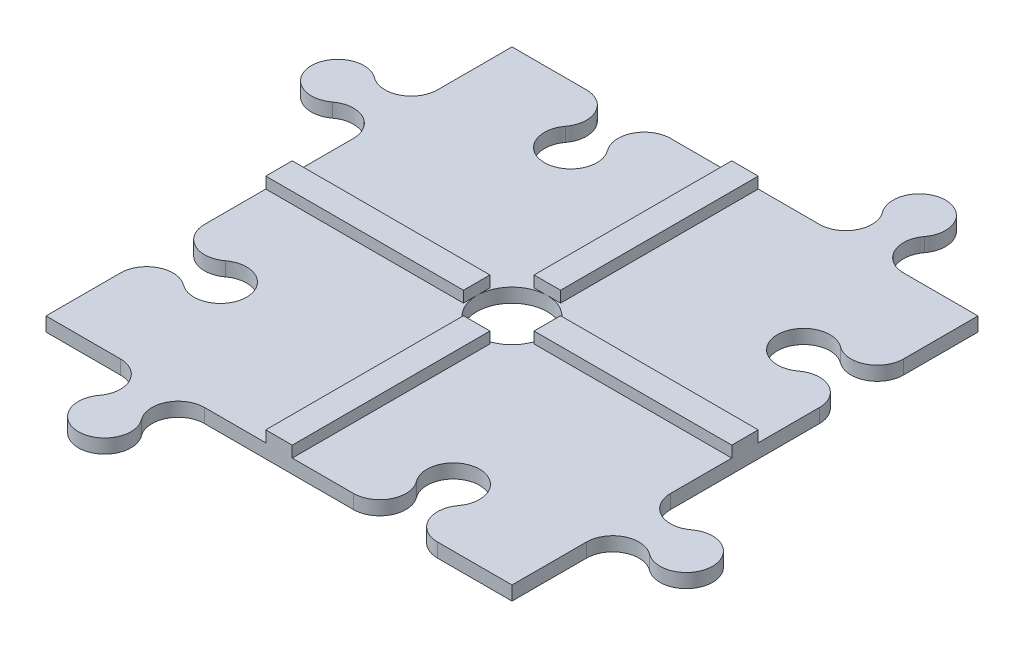
SolidWorks part; units mm, degrees
note: The reader was unsure of these and kept them because the rebuilt part matched: shared geometry of "Sketch2<3>".
ref_plane "Front Plane" through (0, 0, 0) normal (0, 0, 1) x (1, 0, 0)
ref_plane "Top Plane" through (0, 0, 0) normal (0, 1, 0) x (1, 0, 0)
ref_plane "Right Plane" through (0, 0, 0) normal (1, 0, 0) x (0, 0, -1)
sketch "Sketch1" plane through (0, 0, 0) normal (0, 1, 0) x (1, 0, 0)
  line L1 (52.7929, -52.7929) -> (-52.7929, -52.7929)
  line L2 (52.7929, -52.7929) -> (52.7929, 52.7929)
  line L3 (52.7929, 52.7929) -> (-52.7929, 52.7929)
  line L4 (-52.7929, -52.7929) -> (-52.7929, 52.7929)
  line L5 (52.7929, -52.7929) -> (-52.7929, 52.7929) construction
  line L6 (52.7929, 52.7929) -> (-52.7929, -52.7929) construction
  circle A0 centre (0, 0) radius 52.7929 construction
  circle A1 centre (0, 0) radius 52.7929 construction
  dimension "D1" = 105.5858
extrude "Boss-Extrude1" add sketch "Sketch1" along normal blind 3.175 contours L4 L3 L2 L1
sketch "Sketch2" plane through (0, 0, 0) normal (0, 1, 0) x (1, 0, 0)
  line L0 (-52.7929, 26.3965) -> (-113.1129, 26.3965) construction
  line L1 (-52.7929, 35.9215) -> (-52.7929, 16.8715)
  line L2 (-52.7929, -52.7929) -> (-52.7929, 52.7929) construction
  line L3 (0, 0) -> (-52.7929, 0) construction
  line L4 (52.7929, 52.7929) -> (-52.7929, -52.7929) construction
  line L5 (-52.7929, -35.9215) -> (-52.7929, -16.8715)
  arc A0 (-62.3179, 21.634) -> (-71.8429, 26.3965) centre (-65.8898, 26.3965) cw
  arc A1 (-62.3179, 21.634) -> (-52.7929, 16.8715) centre (-58.746, 16.8715) cw
  arc A2 (-62.3179, 31.159) -> (-52.7929, 35.9215) centre (-58.746, 35.9215) ccw
  arc A3 (-62.3179, -21.634) -> (-52.7929, -16.8715) centre (-58.746, -16.8715) ccw construction
  arc A4 (-62.3179, 31.159) -> (-71.8429, 26.3965) centre (-65.8898, 26.3965) ccw
  arc A5 (-62.3179, -21.634) -> (-71.8429, -26.3965) centre (-65.8898, -26.3965) ccw construction
  arc A6 (-62.3179, -31.159) -> (-71.8429, -26.3965) centre (-65.8898, -26.3965) cw construction
  arc A7 (-62.3179, -31.159) -> (-52.7929, -35.9215) centre (-58.746, -35.9215) cw construction
  arc A8 (-43.2679, -31.159) -> (-52.7929, -35.9215) centre (-46.8398, -35.9215) ccw
  arc A9 (-43.2679, -31.159) -> (-33.7429, -26.3965) centre (-39.696, -26.3965) ccw
  arc A10 (-43.2679, -21.634) -> (-33.7429, -26.3965) centre (-39.696, -26.3965) cw
  arc A11 (-43.2679, -21.634) -> (-52.7929, -16.8715) centre (-46.8398, -16.8715) cw
  point P19 (-77.9803, 16.8715)
  point P22 (-77.9803, 35.9215)
  dimension "D1" = 19.05
  dimension "D2" = 19.05
extrude "Boss-Extrude2" add sketch "Sketch2" along normal up to surface (3.175 mm away) contours A0 A4 A2 L1 A1 up to face at (0, 3.175, 0)
extrude "Cut-Extrude2" cut sketch "Sketch2<3>" along normal through all contours L5 A11 A10 A9 A8
sketch "Sketch2<3>" plane through (0, 0, 0) normal (0, 1, 0) x (1, 0, 0) same geometry as "Sketch2"
sketch "Sketch3" [suppressed] plane through (0, 0, 0) normal (0, 0, 1) x (1, 0, 0)
  line L0 (0, 0) -> (0, 29.4045) construction
  line L1 (55.5, 0) -> (-55.5, 0) construction
pattern_circular "CirPattern1" count 4 over 360 about axis through (0, 0, 0) along (0, 1, 0) of "Boss-Extrude2", "Cut-Extrude2"
sketch "Sketch4" plane through (0, 3.175, 0) normal (0, 1, 0) x (1, 0, 0)
  circle A0 centre (0, 0) radius 8.001
  dimension "D1" = 16.002
extrude "Cut-Extrude3" cut sketch "Sketch4" against normal up to surface (3.175 mm away) up to face at (0, 0, 0)
sketch "Sketch5" plane through (0, 3.175, 0) normal (0, 1, 0) x (1, 0, 0)
  line L0 (-52.7929, 3) -> (-7.4173, 3)
  line L1 (-52.7929, -3) -> (-7.4173, -3)
  line L2 (-52.7929, 52.7929) -> (-52.7929, -52.7929)
  line L3 (-35.9215, -52.7929) -> (-52.7929, -52.7929) construction
  line L4 (-52.7929, 0) -> (-8.001, 0) construction
  line L5 (-8.001, 3) -> (-8.001, -3)
  circle A0 centre (0, 0) radius 8.001 construction
  line M27 (-52.7929, 16.8715) -> (-52.7929, -16.8715)
  dimension "D1" = 6
extrude "Boss-Extrude3" add sketch "Sketch5" along normal blind 2.54 contours L4 L2 L1 L5 | L4 L5 L0 M27
pattern_circular "CirPattern2" count 4 over 360 about axis through (0, 0, 0) along (0, 1, 0) of "Boss-Extrude3"
sketch "Sketch6" plane through (0, 3.175, 0) normal (0, 1, 0) x (1, 0, 0)
  line L0 (0, 8.001) -> (-3, 8.001) construction
  line L1 (-3, 8.001) -> (-3, 52.7929) construction
  line L2 (-3, 52.7929) -> (-16.8715, 52.7929) construction
  line L3 (-35.9215, 52.7929) -> (-52.7929, 52.7929) construction
  line L4 (-52.7929, 52.7929) -> (-52.7929, 35.9215) construction
  line L5 (-52.7929, 16.8715) -> (-52.7929, 3) construction
  line L6 (-52.7929, 3) -> (-8.001, 3) construction
  line L7 (-8.001, 3) -> (-8.001, 0) construction
  line L8 (16.8715, 52.7929) -> (3, 52.7929) construction
  line L9 (3, 52.7929) -> (3, 8.001) construction
  line L10 (3, 8.001) -> (0, 8.001) construction
  line L11 (8.001, 0) -> (8.001, 3) construction
  line L12 (8.001, 3) -> (52.7929, 3) construction
  line L13 (52.7929, 3) -> (52.7929, 16.8715) construction
  line L14 (52.7929, 35.9215) -> (52.7929, 52.7929) construction
  line L15 (52.7929, 52.7929) -> (35.9215, 52.7929) construction
  line L16 (52.7929, -16.8715) -> (52.7929, -3) construction
  line L17 (52.7929, -3) -> (8.001, -3) construction
  line L18 (8.001, -3) -> (8.001, 0) construction
  line L19 (0, -8.001) -> (3, -8.001) construction
  line L20 (3, -8.001) -> (3, -52.7929) construction
  line L21 (3, -52.7929) -> (16.8715, -52.7929) construction
  line L22 (35.9215, -52.7929) -> (52.7929, -52.7929) construction
  line L23 (52.7929, -52.7929) -> (52.7929, -35.9215) construction
  line L24 (-16.8715, -52.7929) -> (-3, -52.7929) construction
  line L25 (-3, -52.7929) -> (-3, -8.001) construction
  line L26 (-3, -8.001) -> (0, -8.001) construction
  line L27 (-8.001, 0) -> (-8.001, -3) construction
  line L28 (-8.001, -3) -> (-52.7929, -3) construction
  line L29 (-52.7929, -3) -> (-52.7929, -16.8715) construction
  line L30 (-52.7929, -35.9215) -> (-52.7929, -52.7929) construction
  line L31 (-52.7929, -52.7929) -> (-35.9215, -52.7929) construction
  line L32 (0, 8.001) -> (-3, 8.001)
  line L33 (-3, 8.001) -> (-3, 52.7929)
  line L34 (-3, 52.7929) -> (-16.8715, 52.7929)
  line L35 (-35.9215, 52.7929) -> (-52.7929, 52.7929)
  line L36 (-52.7929, 52.7929) -> (-52.7929, 35.9215)
  line L37 (-52.7929, 16.8715) -> (-52.7929, 3)
  line L38 (-52.7929, 3) -> (-8.001, 3)
  line L39 (-8.001, 3) -> (-8.001, 0)
  line L40 (16.8715, 52.7929) -> (3, 52.7929)
  line L41 (3, 52.7929) -> (3, 8.001)
  line L42 (3, 8.001) -> (0, 8.001)
  line L43 (8.001, 0) -> (8.001, 3)
  line L44 (8.001, 3) -> (52.7929, 3)
  line L45 (52.7929, 3) -> (52.7929, 16.8715)
  line L46 (52.7929, 35.9215) -> (52.7929, 52.7929)
  line L47 (52.7929, 52.7929) -> (35.9215, 52.7929)
  line L48 (52.7929, -16.8715) -> (52.7929, -3)
  line L49 (52.7929, -3) -> (8.001, -3)
  line L50 (8.001, -3) -> (8.001, 0)
  line L51 (0, -8.001) -> (3, -8.001)
  line L52 (3, -8.001) -> (3, -52.7929)
  line L53 (3, -52.7929) -> (16.8715, -52.7929)
  line L54 (35.9215, -52.7929) -> (52.7929, -52.7929)
  line L55 (52.7929, -52.7929) -> (52.7929, -35.9215)
  line L56 (-16.8715, -52.7929) -> (-3, -52.7929)
  line L57 (-3, -52.7929) -> (-3, -8.001)
  line L58 (-3, -8.001) -> (0, -8.001)
  line L59 (-8.001, 0) -> (-8.001, -3)
  line L60 (-8.001, -3) -> (-52.7929, -3)
  line L61 (-52.7929, -3) -> (-52.7929, -16.8715)
  line L62 (-52.7929, -35.9215) -> (-52.7929, -52.7929)
  line L63 (-52.7929, -52.7929) -> (-35.9215, -52.7929)
  arc A1 (-16.8715, 52.7929) -> (-21.634, 43.2679) centre (-16.8715, 46.8398) ccw construction
  arc A2 (-31.159, 43.2679) -> (-21.634, 43.2679) centre (-26.3965, 39.696) ccw construction
  arc A3 (-31.159, 43.2679) -> (-35.9215, 52.7929) centre (-35.9215, 46.8398) ccw construction
  arc A4 (-62.3179, 31.159) -> (-52.7929, 35.9215) centre (-58.746, 35.9215) ccw construction
  arc A5 (-62.3179, 31.159) -> (-62.3179, 21.634) centre (-65.8898, 26.3965) ccw construction
  arc A6 (-52.7929, 16.8715) -> (-62.3179, 21.634) centre (-58.746, 16.8715) ccw construction
  arc A8 (52.7929, 16.8715) -> (43.2679, 21.634) centre (46.8398, 16.8715) ccw construction
  arc A9 (43.2679, 31.159) -> (43.2679, 21.634) centre (39.696, 26.3965) ccw construction
  arc A10 (43.2679, 31.159) -> (52.7929, 35.9215) centre (46.8398, 35.9215) ccw construction
  arc A11 (31.159, 62.3179) -> (35.9215, 52.7929) centre (35.9215, 58.746) ccw construction
  arc A12 (31.159, 62.3179) -> (21.634, 62.3179) centre (26.3965, 65.8898) ccw construction
  arc A13 (16.8715, 52.7929) -> (21.634, 62.3179) centre (16.8715, 58.746) ccw construction
  arc A15 (16.8715, -52.7929) -> (21.634, -43.2679) centre (16.8715, -46.8398) ccw construction
  arc A16 (31.159, -43.2679) -> (21.634, -43.2679) centre (26.3965, -39.696) ccw construction
  arc A17 (31.159, -43.2679) -> (35.9215, -52.7929) centre (35.9215, -46.8398) ccw construction
  arc A18 (62.3179, -31.159) -> (52.7929, -35.9215) centre (58.746, -35.9215) ccw construction
  arc A19 (62.3179, -31.159) -> (62.3179, -21.634) centre (65.8898, -26.3965) ccw construction
  arc A20 (52.7929, -16.8715) -> (62.3179, -21.634) centre (58.746, -16.8715) ccw construction
  arc A22 (-52.7929, -16.8715) -> (-43.2679, -21.634) centre (-46.8398, -16.8715) ccw construction
  arc A23 (-43.2679, -31.159) -> (-43.2679, -21.634) centre (-39.696, -26.3965) ccw construction
  arc A24 (-43.2679, -31.159) -> (-52.7929, -35.9215) centre (-46.8398, -35.9215) ccw construction
  arc A25 (-31.159, -62.3179) -> (-35.9215, -52.7929) centre (-35.9215, -58.746) ccw construction
  arc A26 (-31.159, -62.3179) -> (-21.634, -62.3179) centre (-26.3965, -65.8898) ccw construction
  arc A27 (-16.8715, -52.7929) -> (-21.634, -62.3179) centre (-16.8715, -58.746) ccw construction
  arc A29 (-16.8715, 52.7929) -> (-21.634, 43.2679) centre (-16.8715, 46.8398) ccw
  arc A30 (-31.159, 43.2679) -> (-21.634, 43.2679) centre (-26.3965, 39.696) ccw
  arc A31 (-31.159, 43.2679) -> (-35.9215, 52.7929) centre (-35.9215, 46.8398) ccw
  arc A32 (-62.3179, 31.159) -> (-52.7929, 35.9215) centre (-58.746, 35.9215) ccw
  arc A33 (-62.3179, 31.159) -> (-62.3179, 21.634) centre (-65.8898, 26.3965) ccw
  arc A34 (-52.7929, 16.8715) -> (-62.3179, 21.634) centre (-58.746, 16.8715) ccw
  arc A36 (52.7929, 16.8715) -> (43.2679, 21.634) centre (46.8398, 16.8715) ccw
  arc A37 (43.2679, 31.159) -> (43.2679, 21.634) centre (39.696, 26.3965) ccw
  arc A38 (43.2679, 31.159) -> (52.7929, 35.9215) centre (46.8398, 35.9215) ccw
  arc A39 (31.159, 62.3179) -> (35.9215, 52.7929) centre (35.9215, 58.746) ccw
  arc A40 (31.159, 62.3179) -> (21.634, 62.3179) centre (26.3965, 65.8898) ccw
  arc A41 (16.8715, 52.7929) -> (21.634, 62.3179) centre (16.8715, 58.746) ccw
  arc A43 (16.8715, -52.7929) -> (21.634, -43.2679) centre (16.8715, -46.8398) ccw
  arc A44 (31.159, -43.2679) -> (21.634, -43.2679) centre (26.3965, -39.696) ccw
  arc A45 (31.159, -43.2679) -> (35.9215, -52.7929) centre (35.9215, -46.8398) ccw
  arc A46 (62.3179, -31.159) -> (52.7929, -35.9215) centre (58.746, -35.9215) ccw
  arc A47 (62.3179, -31.159) -> (62.3179, -21.634) centre (65.8898, -26.3965) ccw
  arc A48 (52.7929, -16.8715) -> (62.3179, -21.634) centre (58.746, -16.8715) ccw
  arc A50 (-52.7929, -16.8715) -> (-43.2679, -21.634) centre (-46.8398, -16.8715) ccw
  arc A51 (-43.2679, -31.159) -> (-43.2679, -21.634) centre (-39.696, -26.3965) ccw
  arc A52 (-43.2679, -31.159) -> (-52.7929, -35.9215) centre (-46.8398, -35.9215) ccw
  arc A53 (-31.159, -62.3179) -> (-35.9215, -52.7929) centre (-35.9215, -58.746) ccw
  arc A54 (-31.159, -62.3179) -> (-21.634, -62.3179) centre (-26.3965, -65.8898) ccw
  arc A55 (-16.8715, -52.7929) -> (-21.634, -62.3179) centre (-16.8715, -58.746) ccw
sketch "Sketch7" plane through (0, 3.175, 0) normal (0, 1, 0) x (1, 0, 0)
  line L32 (-16.8715, -52.7929) -> (-3, -52.7929)
  line L33 (-3, -52.7929) -> (-3, -8.001)
  line L34 (-3, -8.001) -> (0, -8.001)
  line L35 (0, -8.001) -> (3, -8.001)
  line L36 (3, -8.001) -> (3, -52.7929)
  line L37 (3, -52.7929) -> (16.8715, -52.7929)
  line L38 (35.9215, -52.7929) -> (52.7929, -52.7929)
  line L39 (52.7929, -52.7929) -> (52.7929, -35.9215)
  line L40 (52.7929, -16.8715) -> (52.7929, -3)
  line L41 (52.7929, -3) -> (8.001, -3)
  line L42 (8.001, -3) -> (8.001, 0)
  line L43 (8.001, 0) -> (8.001, 3)
  line L44 (8.001, 3) -> (52.7929, 3)
  line L45 (52.7929, 3) -> (52.7929, 16.8715)
  line L46 (52.7929, 35.9215) -> (52.7929, 52.7929)
  line L47 (52.7929, 52.7929) -> (35.9215, 52.7929)
  line L48 (16.8715, 52.7929) -> (3, 52.7929)
  line L49 (3, 52.7929) -> (3, 8.001)
  line L50 (3, 8.001) -> (0, 8.001)
  line L51 (0, 8.001) -> (-3, 8.001)
  line L52 (-3, 8.001) -> (-3, 52.7929)
  line L53 (-3, 52.7929) -> (-16.8715, 52.7929)
  line L54 (-35.9215, 52.7929) -> (-52.7929, 52.7929)
  line L55 (-52.7929, 52.7929) -> (-52.7929, 35.9215)
  line L56 (-52.7929, 16.8715) -> (-52.7929, 3)
  line L57 (-52.7929, 3) -> (-8.001, 3)
  line L58 (-8.001, 3) -> (-8.001, 0)
  line L59 (-8.001, 0) -> (-8.001, -3)
  line L60 (-8.001, -3) -> (-52.7929, -3)
  line L61 (-52.7929, -3) -> (-52.7929, -16.8715)
  line L62 (-52.7929, -35.9215) -> (-52.7929, -52.7929)
  line L63 (-52.7929, -52.7929) -> (-35.9215, -52.7929)
  line L64 (-16.8715, -52.7929) -> (16.8715, -52.7929)
  line L70 (35.9215, -52.7929) -> (52.7929, -52.7929)
  line L71 (52.7929, -52.7929) -> (52.7929, -35.9215)
  line L77 (52.7929, -16.8715) -> (52.7929, 16.8715)
  line L78 (52.7929, 35.9215) -> (52.7929, 52.7929)
  line L79 (52.7929, 52.7929) -> (35.9215, 52.7929)
  line L80 (16.8715, 52.7929) -> (-16.8715, 52.7929)
  line L86 (-35.9215, 52.7929) -> (-52.7929, 52.7929)
  line L87 (-52.7929, 52.7929) -> (-52.7929, 35.9215)
  line L88 (-52.7929, 16.8715) -> (-52.7929, -16.8715)
  line L93 (-52.7929, 16.8715) -> (-52.7929, -16.8715)
  line L94 (-52.7929, -35.9215) -> (-52.7929, -52.7929)
  line L95 (-52.7929, -52.7929) -> (-35.9215, -52.7929)
  arc A0 (0, 8.001) -> (-8.001, 0) centre (0, 0) ccw construction
  arc A1 (-8.001, 0) -> (0, -8.001) centre (0, 0) ccw construction
  arc A2 (0, -8.001) -> (8.001, 0) centre (0, 0) ccw construction
  arc A3 (8.001, 0) -> (0, 8.001) centre (0, 0) ccw construction
  arc A4 (0, 8.001) -> (-8.001, 0) centre (0, 0) ccw
  arc A5 (-8.001, 0) -> (0, -8.001) centre (0, 0) ccw
  arc A6 (0, -8.001) -> (8.001, 0) centre (0, 0) ccw
  arc A7 (8.001, 0) -> (0, 8.001) centre (0, 0) ccw
  arc A24 (-16.8715, -52.7929) -> (-21.634, -62.3179) centre (-16.8715, -58.746) ccw
  arc A25 (16.8715, -52.7929) -> (21.634, -43.2679) centre (16.8715, -46.8398) ccw
  arc A26 (31.159, -43.2679) -> (21.634, -43.2679) centre (26.3965, -39.696) ccw
  arc A27 (31.159, -43.2679) -> (35.9215, -52.7929) centre (35.9215, -46.8398) ccw
  arc A28 (62.3179, -31.159) -> (52.7929, -35.9215) centre (58.746, -35.9215) ccw
  arc A29 (62.3179, -31.159) -> (62.3179, -21.634) centre (65.8898, -26.3965) ccw
  arc A30 (52.7929, -16.8715) -> (62.3179, -21.634) centre (58.746, -16.8715) ccw
  arc A31 (52.7929, 16.8715) -> (43.2679, 21.634) centre (46.8398, 16.8715) ccw
  arc A32 (43.2679, 31.159) -> (43.2679, 21.634) centre (39.696, 26.3965) ccw
  arc A33 (43.2679, 31.159) -> (52.7929, 35.9215) centre (46.8398, 35.9215) ccw
  arc A34 (31.159, 62.3179) -> (35.9215, 52.7929) centre (35.9215, 58.746) ccw
  arc A35 (31.159, 62.3179) -> (21.634, 62.3179) centre (26.3965, 65.8898) ccw
  arc A36 (16.8715, 52.7929) -> (21.634, 62.3179) centre (16.8715, 58.746) ccw
  arc A37 (-16.8715, 52.7929) -> (-21.634, 43.2679) centre (-16.8715, 46.8398) ccw
  arc A38 (-31.159, 43.2679) -> (-21.634, 43.2679) centre (-26.3965, 39.696) ccw
  arc A39 (-31.159, 43.2679) -> (-35.9215, 52.7929) centre (-35.9215, 46.8398) ccw
  arc A40 (-62.3179, 31.159) -> (-52.7929, 35.9215) centre (-58.746, 35.9215) ccw
  arc A41 (-62.3179, 31.159) -> (-62.3179, 21.634) centre (-65.8898, 26.3965) ccw
  arc A42 (-52.7929, 16.8715) -> (-62.3179, 21.634) centre (-58.746, 16.8715) ccw
  arc A43 (-52.7929, -16.8715) -> (-43.2679, -21.634) centre (-46.8398, -16.8715) ccw
  arc A44 (-43.2679, -31.159) -> (-43.2679, -21.634) centre (-39.696, -26.3965) ccw
  arc A45 (-43.2679, -31.159) -> (-52.7929, -35.9215) centre (-46.8398, -35.9215) ccw
  arc A46 (-31.159, -62.3179) -> (-35.9215, -52.7929) centre (-35.9215, -58.746) ccw
  arc A47 (-31.159, -62.3179) -> (-21.634, -62.3179) centre (-26.3965, -65.8898) ccw
  arc A48 (-16.8715, -52.7929) -> (-21.634, -62.3179) centre (-16.8715, -58.746) ccw
  arc A49 (16.8715, -52.7929) -> (21.634, -43.2679) centre (16.8715, -46.8398) ccw
  arc A50 (31.159, -43.2679) -> (21.634, -43.2679) centre (26.3965, -39.696) ccw
  arc A51 (31.159, -43.2679) -> (35.9215, -52.7929) centre (35.9215, -46.8398) ccw
  arc A52 (62.3179, -31.159) -> (52.7929, -35.9215) centre (58.746, -35.9215) ccw
  arc A53 (62.3179, -31.159) -> (62.3179, -21.634) centre (65.8898, -26.3965) ccw
  arc A54 (52.7929, -16.8715) -> (62.3179, -21.634) centre (58.746, -16.8715) ccw
  arc A55 (52.7929, 16.8715) -> (43.2679, 21.634) centre (46.8398, 16.8715) ccw
  arc A56 (43.2679, 31.159) -> (43.2679, 21.634) centre (39.696, 26.3965) ccw
  arc A57 (43.2679, 31.159) -> (52.7929, 35.9215) centre (46.8398, 35.9215) ccw
  arc A58 (31.159, 62.3179) -> (35.9215, 52.7929) centre (35.9215, 58.746) ccw
  arc A59 (31.159, 62.3179) -> (21.634, 62.3179) centre (26.3965, 65.8898) ccw
  arc A60 (16.8715, 52.7929) -> (21.634, 62.3179) centre (16.8715, 58.746) ccw
  arc A61 (-16.8715, 52.7929) -> (-21.634, 43.2679) centre (-16.8715, 46.8398) ccw
  arc A62 (-31.159, 43.2679) -> (-21.634, 43.2679) centre (-26.3965, 39.696) ccw
  arc A63 (-31.159, 43.2679) -> (-35.9215, 52.7929) centre (-35.9215, 46.8398) ccw
  arc A64 (-62.3179, 31.159) -> (-52.7929, 35.9215) centre (-58.746, 35.9215) ccw
  arc A65 (-62.3179, 31.159) -> (-62.3179, 21.634) centre (-65.8898, 26.3965) ccw
  arc A66 (-52.7929, 16.8715) -> (-62.3179, 21.634) centre (-58.746, 16.8715) ccw
  arc A67 (-52.7929, -16.8715) -> (-43.2679, -21.634) centre (-46.8398, -16.8715) ccw
  arc A68 (-43.2679, -31.159) -> (-43.2679, -21.634) centre (-39.696, -26.3965) ccw
  arc A69 (-43.2679, -31.159) -> (-52.7929, -35.9215) centre (-46.8398, -35.9215) ccw
  arc A70 (-31.159, -62.3179) -> (-35.9215, -52.7929) centre (-35.9215, -58.746) ccw
  arc A71 (-31.159, -62.3179) -> (-21.634, -62.3179) centre (-26.3965, -65.8898) ccw
  dimension "D1" = 0
